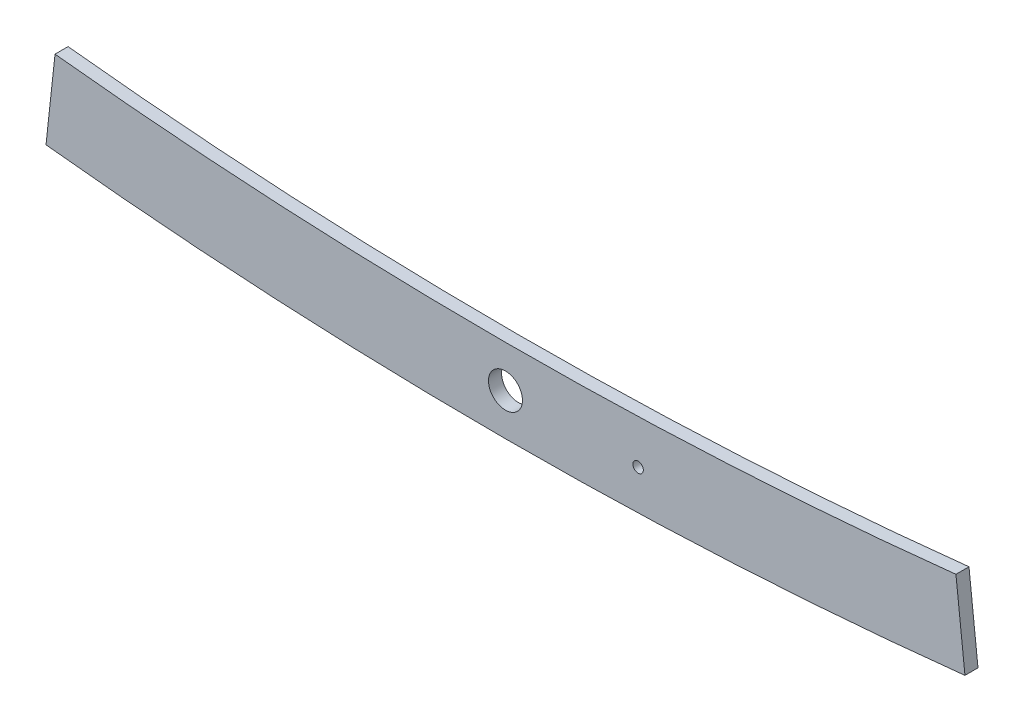
SolidWorks part; units mm, degrees
material "Plain Carbon Steel"
ref_plane "Front Plane" through (0, 0, 0) normal (0, 0, 1) x (1, 0, 0)
ref_plane "Top Plane" through (0, 0, 0) normal (0, 1, 0) x (1, 0, 0)
ref_plane "Right Plane" through (0, 0, 0) normal (1, 0, 0) x (0, 0, -1)
sketch "Sketch1" plane through (0, 0, 0) normal (0, 0, 1) x (1, 0, 0)
  line L0 (88, 4.759) -> (86.2745, 20.6657)
  line L1 (-88, 4.759) -> (-86.2745, 20.6657)
  arc A0 (-88, 4.759) -> (88, 4.759) centre (0, 816) ccw
  arc A1 (-86.2745, 20.6657) -> (86.2745, 20.6657) centre (0, 816) ccw
  dimension "D2" = 816
  dimension "D3" = 800
  dimension "D1" = 816
  dimension "D4" = 88
  dimension "D5" = 88
extrude "Boss-Extrude1" add sketch "Sketch1" along normal mid plane 2.5
sketch "Sketch2" plane through (0, 0, 0) normal (0, 0, 1) x (1, 0, 0)
  circle A0 centre (0, 8) radius 3.25
  dimension "D2" = 6.5
  dimension "D1" = 8
extrude "Cut-Extrude1" cut sketch "Sketch2" against normal mid plane 20
ref_plane "Plane1" through (0, 8, 0) normal (0, 1, 0) x (1, 0, 0)
ref_axis "Axis1" through (0, 8, 1.375) along (0, 0, -1)
sketch "Sketch3" plane through (0, 0, 0) normal (0, 0, 1) x (1, 0, 0)
  line L0 (1.375, 8) -> (-1.375, 8) construction
  circle A0 centre (25.4, 8) radius 1
  dimension "D3" = 2
  dimension "D1" = 25.4
  dimension "D2" = 8
extrude "Cut-Extrude2" cut sketch "Sketch3" against normal mid plane 20
ref_plane "Plane2" through (25.4, 0, 0) normal (1, 0, 0) x (0, 0, -1)
ref_plane "Plane3" through (0, 8.3994, 0) normal (0, 1, 0) x (1, 0, 0)
ref_axis "Axis2" through (25.4, 8.3994, 1.375) along (0, 0, -1)
